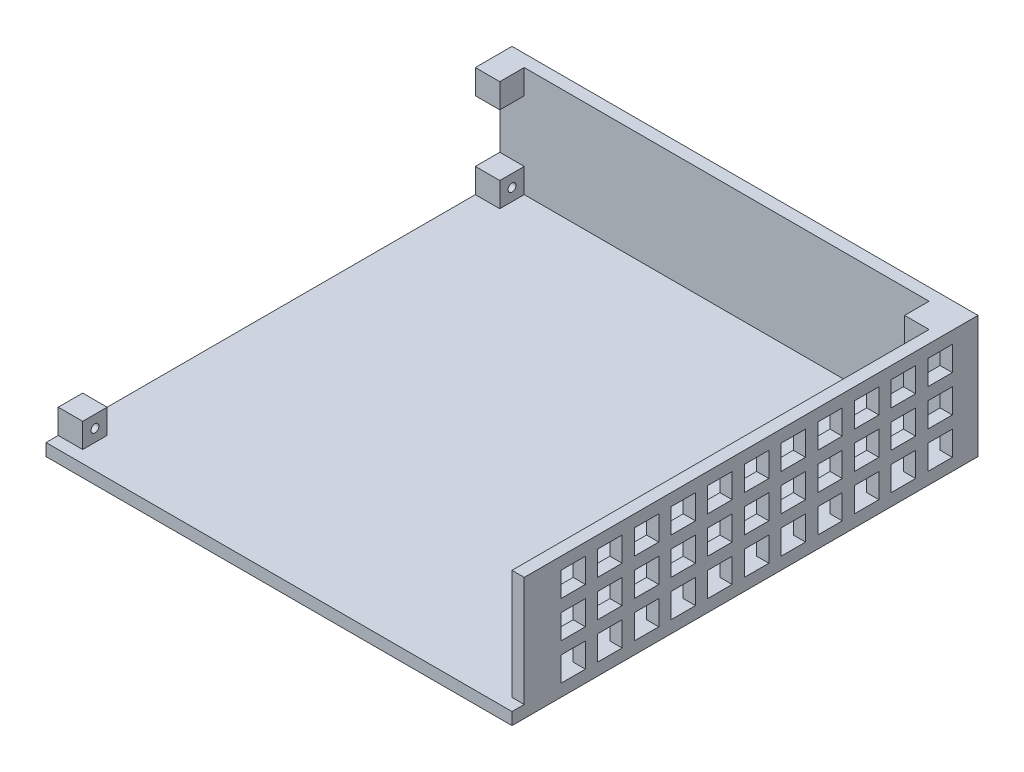
SolidWorks part; units mm, degrees
ref_plane "Front Plane" through (0, 0, 0) normal (0, 0, 1) x (1, 0, 0)
ref_plane "Top Plane" through (0, 0, 0) normal (0, 1, 0) x (1, 0, 0)
ref_plane "Right Plane" through (0, 0, 0) normal (1, 0, 0) x (0, 0, -1)
sketch "Sketch1" plane through (0, 0, 0) normal (0, 1, 0) x (1, 0, 0)
  line L1 (-95.25, 95.25) -> (95.25, 95.25)
  line L2 (-95.25, 95.25) -> (-95.25, -95.25)
  line L3 (-95.25, -95.25) -> (95.25, -95.25)
  line L4 (95.25, 95.25) -> (95.25, -95.25)
  line L5 (-95.25, 95.25) -> (95.25, -95.25) construction
  line L6 (-95.25, -95.25) -> (95.25, 95.25) construction
  point P0 (0, 0)
  dimension "D1" = 190.5
  dimension "D2" = 190.5
extrude "Boss-Extrude1" add sketch "Sketch1" along normal blind 5
sketch "Sketch9" plane through (0, 5, 0) normal (0, 1, 0) x (1, 0, 0)
  line L0 (95.25, -95.25) -> (95.25, 95.25) construction
  line L1 (-95.25, 95.25) -> (95.25, 95.25)
  line L2 (-95.25, 95.25) -> (-95.25, 90.25)
  line L3 (-95.25, 90.25) -> (95.25, 90.25)
  line L4 (95.25, 95.25) -> (95.25, 90.25)
  dimension "D1" = 5
extrude "Boss-Extrude5" add sketch "Sketch9" along normal blind 45
sketch "Sketch10" plane through (0, 5, 0) normal (0, 1, 0) x (1, 0, 0)
  line L0 (-95.25, -95.25) -> (95.25, -95.25) construction
  line L1 (95.25, 90.25) -> (90.25, 90.25)
  line L2 (95.25, 90.25) -> (95.25, -95.25)
  line L3 (95.25, -95.25) -> (90.25, -95.25)
  line L4 (90.25, 90.25) -> (90.25, -95.25)
  dimension "D1" = 5
extrude "Boss-Extrude6" add sketch "Sketch10" along normal up to surface (45 mm away) up to face at (0, 50, -92.75)
sketch "Sketch11" plane through (95.25, 0, 0) normal (1, 0, 0) x (0, 0, -1)
  line L0 (-95.25, 50) -> (95.25, 50) construction
  line L1 (-65.25, 45) -> (-75.25, 45)
  line L2 (-65.25, 45) -> (-65.25, 35)
  line L3 (-65.25, 35) -> (-75.25, 35)
  line L4 (-75.25, 45) -> (-75.25, 35)
  line L5 (-95.25, 50) -> (-95.25, 0) construction
  dimension "D1" = 5
  dimension "D2" = 20
  dimension "D3" = 10
  dimension "D4" = 10
extrude "Cut-Extrude3" cut sketch "Sketch11" against normal up to surface (5 mm away) up to face at (90.25, 27.5, 2.5)
pattern_linear "LPattern3" count 3 spacing 15 along (0, -1, 0) of "Cut-Extrude3"
pattern_linear "LPattern4" count 11 spacing 15 along (0, 0, -1) of "LPattern3"
sketch "Sketch12" plane through (-95.25, 0, 0) normal (-1, 0, 0) x (0, 0, 1)
  line L1 (-90.25, 5) -> (-80.25, 5)
  line L2 (-90.25, 5) -> (-90.25, 15)
  line L3 (-90.25, 15) -> (-80.25, 15)
  line L4 (-80.25, 5) -> (-80.25, 15)
  point P8 (0, 0)
  dimension "D1" = 10
  dimension "D2" = 10
extrude "Boss-Extrude7" add sketch "Sketch12" against normal blind 10
mirror "Mirror1" about plane through (0, 0, 0) normal (0, 0, 1) of "Boss-Extrude7"
sketch "Sketch13" plane through (0, 50, 0) normal (0, 1, 0) x (1, 0, 0)
  line L0 (90.25, 90.25) -> (90.25, -95.25) construction
  line L1 (95.25, -95.25) -> (90.25, -95.25)
  line L2 (95.25, -95.25) -> (95.25, -90.25)
  line L3 (95.25, -90.25) -> (90.25, -90.25)
  line L4 (90.25, -95.25) -> (90.25, -90.25)
  dimension "D1" = 5
extrude "Cut-Extrude4" cut sketch "Sketch13" against normal up to surface (45 mm away) up to face at (65.5463, 5, -0.3426)
sketch "Sketch14" plane through (-95.25, 0, 0) normal (-1, 0, 0) x (0, 0, 1)
  line L0 (80.25, 15) -> (90.25, 15) construction
  line L1 (80.25, 5) -> (80.25, 15) construction
  circle A0 centre (85.25, 10) radius 1.625
  point P4 (85.25, 15)
  point P7 (80.25, 10)
  dimension "D1" = 3.25
extrude "Cut-Extrude5" cut sketch "Sketch14" against normal up to surface (10 mm away) up to face at (-85.25, 10, 85.25)
mirror "Mirror2" about plane through (0, 0, 0) normal (0, 0, 1) of "Cut-Extrude5"
sketch "Sketch15" plane through (0, 0, -90.25) normal (0, 0, 1) x (1, 0, 0)
  line L1 (-95.25, 50) -> (-85.25, 50)
  line L2 (-95.25, 50) -> (-95.25, 40)
  line L3 (-95.25, 40) -> (-85.25, 40)
  line L4 (-85.25, 50) -> (-85.25, 40)
  line L5 (90.25, 50) -> (80.25, 50)
  line L6 (90.25, 50) -> (90.25, 40)
  line L7 (90.25, 40) -> (80.25, 40)
  line L8 (80.25, 50) -> (80.25, 40)
  dimension "D1" = 10
  dimension "D2" = 10
extrude "Boss-Extrude8" add sketch "Sketch15" along normal blind 10
